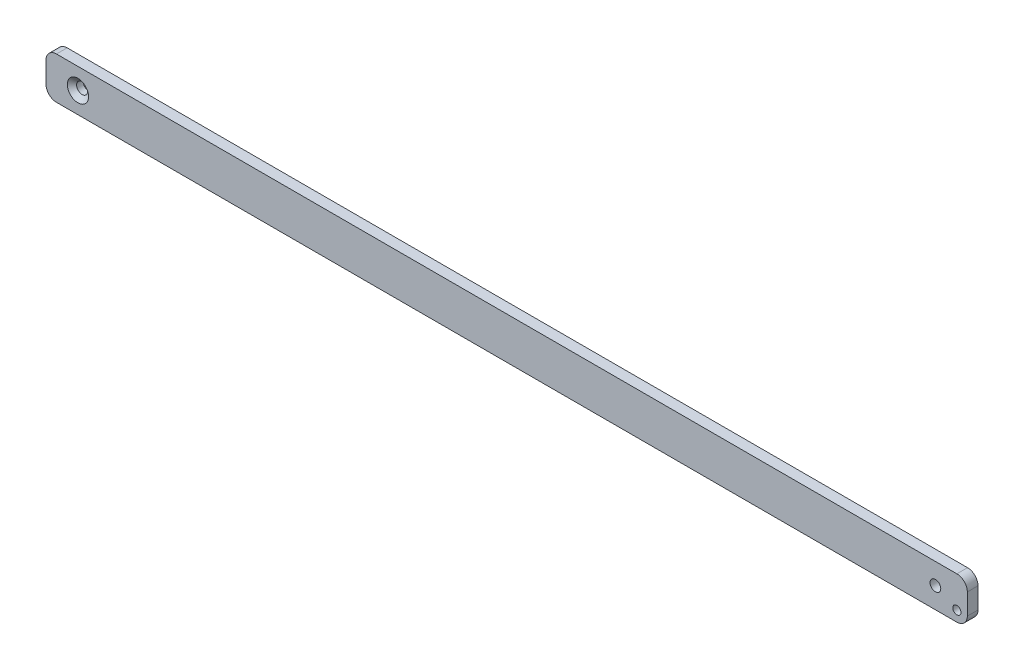
SolidWorks part; units mm, degrees
material "PC High Viscosity"
ref_plane "Front Plane" through (0, 0, 0) normal (0, 0, 1) x (1, 0, 0)
ref_plane "Top Plane" through (0, 0, 0) normal (0, 1, 0) x (1, 0, 0)
ref_plane "Right Plane" through (0, 0, 0) normal (1, 0, 0) x (0, 0, -1)
sketch "Sketch1" plane through (0, 0, 0) normal (0, 0, 1) x (1, 0, 0)
  line L1 (0, 0) -> (40.5308, 0)
  line L2 (0, 0) -> (0, 25.4)
  line L3 (0, 25.4) -> (40.5307, 25.4)
  line L4 (558.8, 0) -> (558.8, 25.4)
  line L11 (558.8, 10.0162) -> (552.45, 13.6823) construction
  line L12 (552.45, 13.6823) -> (546.1, 10.0162) construction
  line L13 (546.1, 10.0162) -> (546.1, 2.6838) construction
  line L14 (546.1, 2.6838) -> (552.45, -0.9823) construction
  line L15 (552.45, -0.9823) -> (558.8, 2.6838) construction
  line L16 (558.8, 2.6838) -> (558.8, 10.0162) construction
  line L19 (40.5307, 25.4) -> (558.8, 25.4)
  line L20 (40.5308, 0) -> (343.7103, 0)
  line L24 (343.7103, 0) -> (558.8, 0)
  circle A0 centre (552.45, 6.35) radius 2.4892
  circle A1 centre (552.45, 6.35) radius 6.35 construction
  dimension "D5" = 4.9784
  dimension "D7" = 12.7
  dimension "D1" = 558.8
  dimension "D2" = 25.4
extrude "Boss-Extrude1" add sketch "Sketch1" along normal blind 6.477 contours L3 | L1 L4 L3 L2 A0 | L1 region at (279.025, 12.7087, 0)
fillet "Fillet2" radius 6.35 4 edges at (558.8, 25.4, 3.2385) (558.8, 0, 3.2385) (0, 0, 3.2385) (0, 25.4, 3.2385)
sketch "Sketch2" plane through (0, 0, 6.477) normal (0, 0, 1) x (1, 0, 0)
  line L2 (558.8, 6.35) -> (558.8, 19.05) construction
  line L3 (6.35, 25.4) -> (552.45, 25.4) construction
  circle A0 centre (539.4325, 12.7) radius 3.2639
  dimension "D1" = 6.5278
  dimension "D2" = 19.3675
  dimension "D3" = 12.7
hole_wizard "CSK for 1/4 Flat Head Machine Screw (100)2" positions "Sketch6" profile "Sketch7" countersink size "1/4" standard "ANSI Inch"
sketch "Sketch6" plane through (0, 0, 6.477) normal (0, 0, 1) x (1, 0, 0)
  line L2 (0, 6.35) -> (0, 19.05) construction
  line L3 (6.35, 0) -> (552.45, 0) construction
  point P0 (19.3675, 12.7)
  point P11 (19.3675, 12.7)
  dimension "D1" = 19.3675
  dimension "D2" = 12.7
sketch "Sketch7" plane through (19.3675, 12.7, 6.477) normal (1, 0, 0) x (0, -1, 0)
  line L0 (0, 0) -> (0, 21.0798)
  line L1 (0, 21.0798) -> (3.3782, 19.05)
  line L2 (3.3782, 19.05) -> (3.3782, 2.5682)
  line L3 (3.3782, 2.5682) -> (6.4389, 0)
  line L5 (6.4389, 0) -> (0, 0)
  line L6 (-3.3782, 2.5682) -> (-6.4389, 0) construction
  line L10 (0, 21.0798) -> (-3.3782, 19.05) construction
  line L11 (0, -6.35) -> (0, 107.95) construction
  dimension "Hole Dia." = 6.7564
  dimension "Hole Depth" = 19.05
  dimension "Near C'Sink Dia." = 12.8778
  dimension "Near C'Sink Angle" = 100
  dimension "Drill Angle" = 118
extrude "Cut-Extrude1" cut sketch "Sketch2" against normal through all
